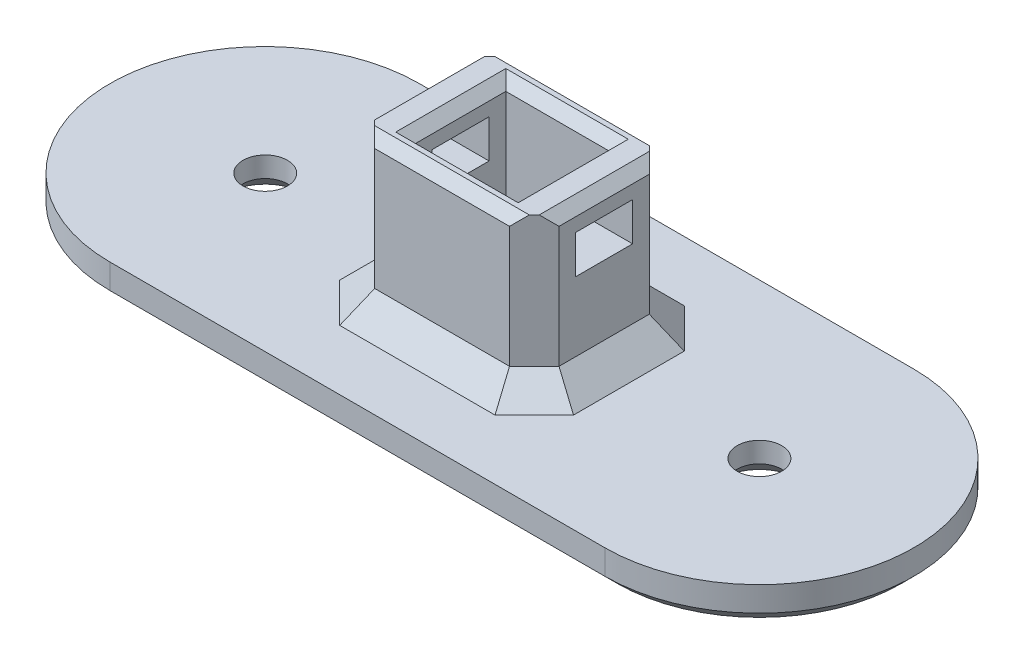
SolidWorks part; units mm, degrees
ref_plane "Front Plane" through (0, 0, 0) normal (0, 0, 1) x (1, 0, 0)
ref_plane "Top Plane" through (0, 0, 0) normal (0, 1, 0) x (1, 0, 0)
ref_plane "Right Plane" through (0, 0, 0) normal (1, 0, 0) x (0, 0, -1)
sketch "Sketch2" plane through (0, 12, 0) normal (0, -1, 0) x (1, 0, 0)
  line L8 (5.45, 3.45) -> (5.45, -3.45) construction
  line L9 (-7.45, -5.65) -> (7.45, -5.65)
  line L10 (-7.45, -5.65) -> (-7.45, 5.65)
  line L11 (-7.45, 5.65) -> (7.45, 5.65)
  line L12 (4.15, -3.65) -> (4.15, 3.65)
  line L13 (4.15, 3.65) -> (-4.15, 3.65)
  line L14 (-4.15, 3.65) -> (-4.15, -3.65)
  line L15 (-4.15, -3.65) -> (4.15, -3.65)
  line L16 (4.15, -3.65) -> (4.15, 3.65)
  line L17 (4.15, 3.65) -> (-4.15, 3.65)
  line L18 (-4.15, 3.65) -> (-4.15, -3.65)
  line L19 (-4.15, -3.65) -> (4.15, -3.65)
  line L20 (7.45, -5.65) -> (7.45, 5.65)
  line L21 (0, 5.65) -> (0, -5.65) construction
  line L22 (-7.45, 0) -> (7.45, 0) construction
  point P0 (0, 0)
  dimension "D2" = 2
  dimension "D3" = 2
  dimension "D4" = 8.3
  dimension "D5" = 7.3
  dimension "D1" = 0.2
extrude "Boss-Extrude1" add sketch "Sketch2" along normal offset from surface (12.6 mm away) 0.6 offset beyond the face yes
sketch "Sketch4" plane through (0, 0, 0) normal (1, 0, 0) x (0, 0, -1)
  line L1 (-1.6, 9.8) -> (-1.6, 8) construction
  line L2 (1.6, 8) -> (1.6, 9.8) construction
  line L3 (2.75, 8) -> (1.6, 8) construction
  line L4 (-1.6, 8) -> (-2.75, 8) construction
  line L5 (-2.75, 8) -> (-2.75, 12) construction
  line L6 (-2.75, 12) -> (-3.45, 12) construction
  line L7 (-3.45, 12) -> (-3.45, 0) construction
  line L8 (-3.45, 0) -> (3.45, 0) construction
  line L9 (3.45, 0) -> (3.45, 12) construction
  line L10 (3.45, 12) -> (2.75, 12) construction
  line L11 (2.75, 12) -> (2.75, 8) construction
  line L13 (-1.6, 9.8) -> (-1.6, 8) construction
  line L14 (1.6, 8) -> (1.6, 9.8) construction
  line L15 (2.75, 8) -> (1.6, 8) construction
  line L16 (-1.6, 8) -> (-2.75, 8) construction
  line L17 (-2.75, 8) -> (-2.75, 12) construction
  line L18 (-2.75, 12) -> (-3.45, 12) construction
  line L19 (-3.45, 12) -> (-3.45, 0) construction
  line L20 (-3.45, 0) -> (3.45, 0) construction
  line L21 (3.45, 0) -> (3.45, 12) construction
  line L22 (3.45, 12) -> (2.75, 12) construction
  line L23 (2.75, 12) -> (2.75, 8) construction
  line L24 (0, -990) -> (0, 49010) construction
  line L25 (-2.3, 10.1) -> (2.3, 10.1)
  line L26 (-2.3, 10.1) -> (-2.3, 7)
  line L27 (-2.3, 7) -> (2.3, 7)
  line L28 (1.6, 10) -> (-1.6, 10)
  line L29 (-1.6, 10) -> (-1.6, 9.8)
  line L30 (-1.6, 9.8) -> (1.6, 9.8)
  line L31 (1.6, 9.8) -> (1.6, 10)
  line L32 (1.6, 10) -> (-1.6, 10) construction
  line L33 (-1.6, 10) -> (-1.6, 9.8) construction
  line L34 (2.3, 10.1) -> (2.3, 7)
  line L35 (1.6, 9.8) -> (1.6, 10) construction
  point P20 (0, 10)
  dimension "D2" = 0.7
  dimension "D3" = 0.1
  dimension "D4" = 1
  dimension "D1" = 0
extrude "Cut-Extrude1" cut sketch "Sketch4" against normal through all both and the other way through all
sketch "Sketch5" plane through (0, -0.6, 0) normal (0, -1, 0) x (1, 0, 0)
  line L0 (-20, 0) -> (20, 0) construction
  line L1 (-20, 12.5) -> (20, 12.5)
  line L2 (-20, -12.5) -> (20, -12.5)
  arc A0 (-20, 12.5) -> (-20, -12.5) centre (-20, 0) ccw
  arc A1 (20, -12.5) -> (20, 12.5) centre (20, 0) ccw
  point P2 (0, 0)
  dimension "D1" = 25
  dimension "D2" = 40
extrude "Boss-Extrude2" add sketch "Sketch5" along normal blind 3
sketch "Sketch7" plane through (0, -0.6, 0) normal (0, 1, 0) x (1, 0, 0)
  line L0 (-20, -10.5) -> (20, -10.5)
  line L1 (20, 10.5) -> (-20, 10.5)
  line L2 (-20, -12.5) -> (20, -12.5)
  line L3 (20, 12.5) -> (-20, 12.5)
  line L4 (-20, -12.5) -> (20, -12.5)
  line L5 (20, 12.5) -> (-20, 12.5)
  arc A0 (20, -10.5) -> (20, 10.5) centre (20, 0) ccw
  arc A1 (-20, 10.5) -> (-20, -10.5) centre (-20, 0) ccw
  arc A2 (-20, 12.5) -> (-20, -12.5) centre (-20, 0) ccw
  arc A3 (20, -12.5) -> (20, 12.5) centre (20, 0) ccw
  arc A4 (-20, 12.5) -> (-20, -12.5) centre (-20, 0) ccw
  arc A5 (20, -12.5) -> (20, 12.5) centre (20, 0) ccw
  dimension "D1" = 0
  dimension "D2" = 2
chamfer "Chamfer1" distance 1 angle 45 4 edges at (32.5, -3.6, 0) (0, -3.6, 12.5) (0, -3.6, -12.5) (-32.5, -3.6, 0)
chamfer "Chamfer2" distance 0.8 angle 45 8 edges at (-7.45, 12, 0) (0, 12, -5.65) (7.45, 12, 0) (0, 12, 5.65) (0, 12, 3.65) (4.15, 12, 0) (0, 12, -3.65) (-4.15, 12, 0)
chamfer "Chamfer3" distance 2 angle 45 4 edges at (-7.45, 5.3, 5.65) (-7.45, 5.3, -5.65) (7.45, 5.3, -5.65) (7.45, 5.3, 5.65)
sketch "Sketch8" plane through (0, -3.6, 0) normal (0, -1, 0) x (1, 0, 0)
  line L0 (-20, 0) -> (20, 0) construction
  point P4 (0, 0)
  point P6 (-20, 0)
  point P7 (20, 0)
  dimension "D1" = 40
hole_wizard "CSK for M3 Flat Head Machine Screw1" positions "Sketch9" profile "Sketch10" countersink size "M3" standard "ANSI Metric" end condition through all
sketch "Sketch9" plane through (0, -3.6, 0) normal (0, -1, 0) x (-1, 0, 0)
  point P0 (-20, 0)
  point P2 (19.9489, 0)
sketch "Sketch10" plane through (20, -3.6, 0) normal (1, 0, 0) x (0, 0, -1)
  line L0 (0, 0) -> (0, 15.6)
  line L1 (0, 15.6) -> (1.8, 15.6)
  line L2 (1.8, 15.6) -> (1.8, 1.35)
  line L3 (1.8, 1.35) -> (3.15, 0)
  line L5 (3.15, 0) -> (0, 0)
  line L6 (-1.8, 1.35) -> (-3.15, 0) construction
  line L11 (0, -6.35) -> (0, 107.95) construction
  dimension "Thru Hole Dia." = 3.6
  dimension "Thru Hole Depth" = 15.6
  dimension "Near C'Sink Dia." = 6.3
  dimension "Near C'Sink Angle" = 90
chamfer "Chamfer4" distance 2 angle 45 8 edges at (-6.45, -0.6, -4.65) (-7.45, -0.6, 0) (0, -0.6, -5.65) (6.45, -0.6, -4.65) (7.45, -0.6, 0) (6.45, -0.6, 4.65) (-6.45, -0.6, 4.65) (0, -0.6, 5.65)
equation "\"case_length\"= 140"
equation "\"plate_thickness\"= 3"
equation "\"D1@Boss-Extrude2\"=\"plate_thickness\""
equation "\"case_height\"= 25"
equation "\"case_width\"= 65"
equation "\"case_to_shell_offset\"= 19.6"
equation "\"body_tip_distance\"= 30"
equation "\"D2@Sketch5\"=\"case_width\"-\"case_height\""
equation "\"D1@Sketch5\"=\"case_height\""
equation "\"D1@Sketch8\"=\"case_width\"-\"case_height\""
